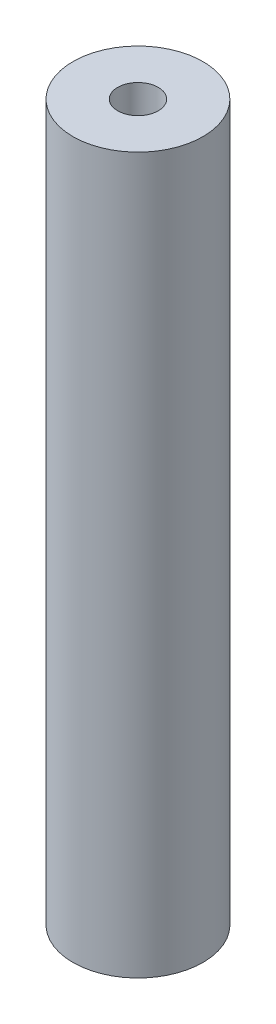
SolidWorks part; units mm, degrees
ref_plane "Front Plane" through (0, 0, 0) normal (0, 0, 1) x (1, 0, 0)
ref_plane "Top Plane" through (0, 0, 0) normal (0, 1, 0) x (1, 0, 0)
ref_plane "Right Plane" through (0, 0, 0) normal (1, 0, 0) x (0, 0, -1)
sketch "Sketch1" plane through (0, 0, 0) normal (0, 1, 0) x (1, 0, 0)
  circle A0 centre (0, 0) radius 4
  dimension "D1" = 8
extrude "Boss-Extrude1" add sketch "Sketch1" along normal blind 44
hole_wizard "Tap Drill for M3 Tap1" positions "Sketch2" profile "Sketch4" hole size "M3" standard "DIN" end condition through all
sketch "Sketch2" plane through (0, 44, 0) normal (0, 1, 0) x (1, 0, 0)
  point P0 (0, 0)
sketch "Sketch4" plane through (0, 44, 0) normal (1, 0, 0) x (0, 0, 1)
  line L0 (0, 0) -> (0, 44)
  line L1 (0, 44) -> (1.25, 44)
  line L2 (1.25, 44) -> (1.25, 0)
  line L5 (1.25, 0) -> (0, 0)
  line L11 (0, -6.35) -> (0, 107.95) construction
  dimension "Thru Hole Dia." = 2.5
  dimension "Thru Hole Depth" = 44
